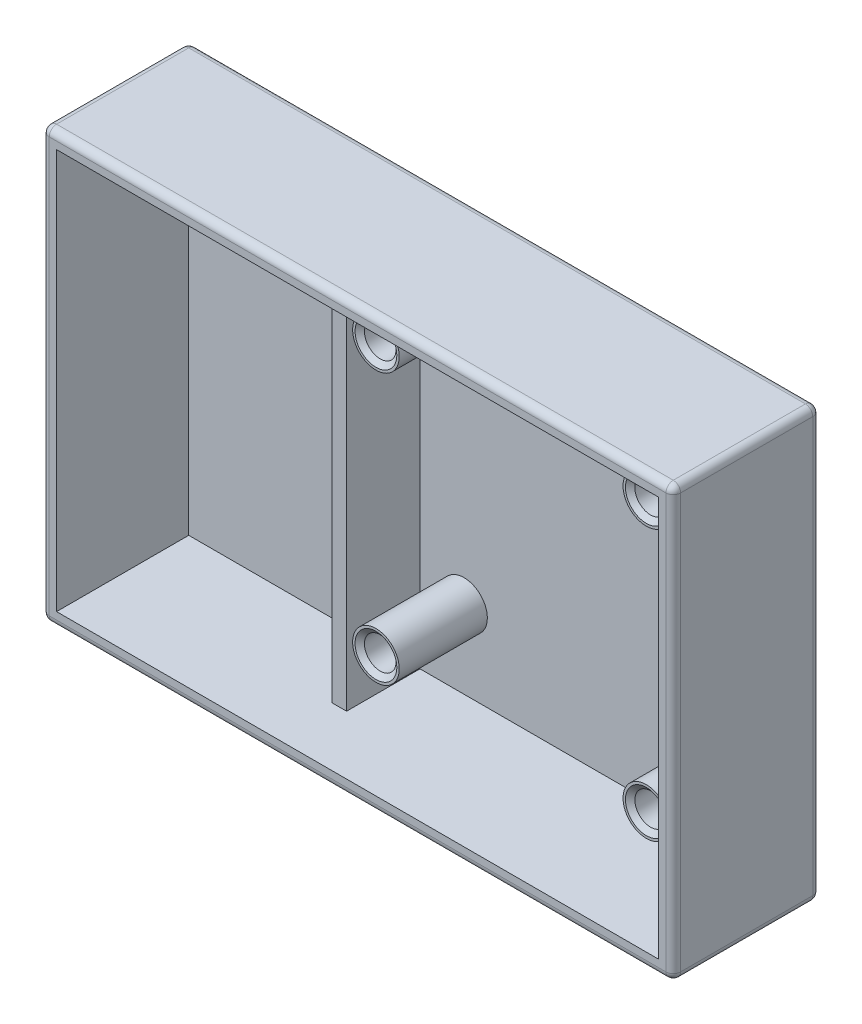
SolidWorks part; units mm, degrees
ref_plane "Front Plane" through (0, 0, 0) normal (0, 0, 1) x (1, 0, 0)
ref_plane "Top Plane" through (0, 0, 0) normal (0, 1, 0) x (1, 0, 0)
ref_plane "Right Plane" through (0, 0, 0) normal (1, 0, 0) x (0, 0, -1)
sketch "Sketch1" plane through (0, 0, 0) normal (0, 0, 1) x (1, 0, 0)
  line L1 (0, 0) -> (86, 0)
  line L2 (0, 0) -> (0, 58.5)
  line L3 (0, 58.5) -> (86, 58.5)
  line L4 (86, 0) -> (86, 58.5)
  dimension "D1" = 86
  dimension "D2" = 58.5
extrude "Boss-Extrude1" add sketch "Sketch1" along normal blind 20
shell "Shell1" thickness 2 removed face at (43, 29.25, 20)
sketch "Sketch4" plane through (0, 0, 2) normal (0, 0, 1) x (1, 0, 0)
  line L0 (84, 56.5) -> (2, 56.5) construction
  line L1 (31.5, 56.5) -> (33.5, 56.5)
  line L2 (31.5, 56.5) -> (31.5, 2)
  line L3 (31.5, 2) -> (33.5, 2)
  line L4 (33.5, 56.5) -> (33.5, 2)
  line L5 (2, 2) -> (84, 2) construction
  dimension "D1" = 2
  dimension "D2" = 29.5
extrude "Boss-Extrude2" add sketch "Sketch4" along normal blind 10 contours L2 L1 L4 L3
fillet "Fillet2" radius 1 7 edges at (43, 58.5, 20) (0, 58.5, 10) (43, 58.5, 0) (86, 0, 10) (86, 29.25, 20) (86, 58.5, 10) (86, 29.25, 0)
fillet "Fillet3" radius 1 9 edges at (85.7071, 0.2929, 19.7071) (85.7071, 0.2929, 0.2929) (0.2929, 58.2071, 0.2929) (0.2929, 58.2071, 19.7071) (42.5, 0, 20) (42.5, 0, 0) (0, 0, 10) (0, 28.75, 0) (0, 28.75, 20)
sketch "Sketch22" plane through (0, 0, 0) normal (0, 0, 1) x (1, 0, 0)
  line L6 (84, 56.5) -> (33.5, 56.5) construction
  line L11 (33.5, 56.5) -> (33.5, 2) construction
  line L12 (33.5, 56.5) -> (33.5, 2) construction
  circle A4 centre (39.5, 49.415) radius 3.175
  circle A5 centre (76.33, 49.415) radius 3.175
  circle A6 centre (39.5, 12.585) radius 3.175
  circle A7 centre (76.33, 12.585) radius 3.175
  dimension "D17" = 6
  dimension "D2" = 36.83
  dimension "D11" = 36.83
  dimension "D12" = 36.83
  dimension "D13" = 36.83
  dimension "D14" = 7.085
  dimension "D15" = 7.085
  dimension "D16" = 6
extrude "Boss-Extrude10" add sketch "Sketch22" along normal blind 14 separate body contours A6 | A4 | A5 | A7
hole_wizard "#4 (0.209) Diameter Hole3" positions "Sketch27" profile "Sketch28" hole size "#4" standard "ANSI Inch"
sketch "Sketch27" plane through (0, 0, 14) normal (0, 0, 1) x (1, 0, 0)
  circle A0 centre (39.5, 49.415) radius 3.175 construction
  circle A1 centre (76.33, 49.415) radius 3.175 construction
  circle A2 centre (39.5, 12.585) radius 3.175 construction
  circle A3 centre (76.33, 12.585) radius 3.175 construction
  point P0 (39.5, 49.415)
  point P2 (39.5, 12.585)
  point P4 (76.33, 12.585)
  point P6 (76.33, 49.415)
  dimension "D1" = 0
  dimension "D2" = 0
  dimension "D3" = 0
  dimension "D4" = 0
  dimension "D5" = 0
  dimension "D6" = 0
sketch "Sketch28" plane through (39.5, 49.415, 14) normal (1, 0, 0) x (0, -1, 0)
  line L0 (0, 0) -> (0, 13.7896)
  line L1 (0, 13.7896) -> (2.1463, 12.5)
  line L2 (2.1463, 12.5) -> (2.1463, 0.5861)
  line L3 (2.1463, 0.5861) -> (2.8448, 0)
  line L5 (2.8448, 0) -> (0, 0)
  line L6 (-2.1463, 0.5861) -> (-2.8448, 0) construction
  line L10 (0, 13.7896) -> (-2.1463, 12.5) construction
  line L11 (0, -6.35) -> (0, 107.95) construction
  dimension "Hole Dia." = 4.2926
  dimension "Hole Depth" = 12.5
  dimension "Near C'Sink Dia." = 5.6896
  dimension "Near C'Sink Angle" = 100
  dimension "Drill Angle" = 118
